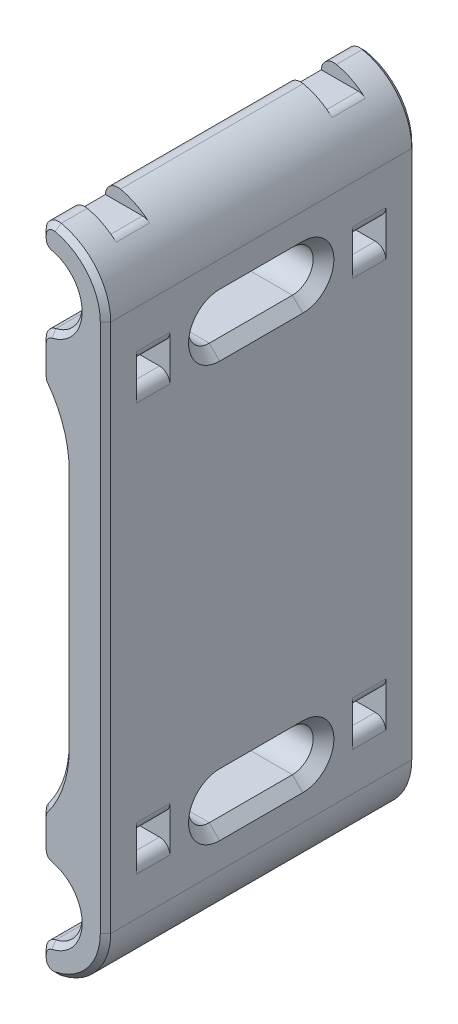
SolidWorks part; units mm, degrees
material "ABS"
ref_plane "Alzado" through (0, 0, 0) normal (0, 0, 1) x (1, 0, 0)
ref_plane "Planta" through (0, 0, 0) normal (0, 1, 0) x (1, 0, 0)
ref_plane "Vista lateral" through (0, 0, 0) normal (1, 0, 0) x (0, 0, -1)
sketch "Croquis1" plane through (0, 0, 0) normal (0, 0, 1) x (1, 0, 0)
  line L5 (-13.465, 0) -> (13.8234, 0) construction
  line L8 (-4, 17.4338) -> (-8.9869, 20.2963)
  line L9 (-4, 17.4338) -> (-4, -17.4338)
  line L10 (0, 25.5) -> (0, -25.5)
  line L11 (-4, -17.4338) -> (-8.9869, -20.2963)
  circle A0 centre (-6, 25.5) radius 3.25
  arc A5 (0, 25.5) -> (-8.9869, 20.2963) centre (-6, 25.5) ccw
  arc A6 (0, -25.5) -> (-8.9869, -20.2963) centre (-6, -25.5) cw
  circle A7 centre (-6, -25.5) radius 3.25
  point P7 (0, 0)
  point P15 (0, 0)
  point P16 (-4, 0)
  point P17 (-4, 0)
  dimension "D1" = 6.5
  dimension "D2" = 51
  dimension "D3" = 4
  dimension "D4" = 6
extrude "Saliente-Extruir1" add sketch "Croquis1" against normal blind 30
fillet "Redondeo1" radius 10 2 edges at (-4, -17.4338, -15) (-4, 17.4338, -15)
sketch "Croquis2" plane through (0, 0, 0) normal (1, 0, 0) x (0, 0, -1)
  line L0 (-8.2811, 0) -> (45.0775, 0) construction
  line L1 (11, 20) -> (19, 20) construction
  line L2 (11, 22) -> (19, 22)
  line L3 (11, 18) -> (19, 18)
  line L4 (11, -20) -> (19, -20) construction
  line L5 (11, -22) -> (19, -22)
  line L6 (11, -18) -> (19, -18)
  line L7 (0, 11.6436) -> (30, 11.6436) construction
  line L8 (30, 31.5) -> (0, 31.5) construction
  arc A0 (11, 22) -> (11, 18) centre (11, 20) ccw
  arc A1 (19, 18) -> (19, 22) centre (19, 20) ccw
  arc A2 (11, -22) -> (11, -18) centre (11, -20) cw
  arc A3 (19, -18) -> (19, -22) centre (19, -20) cw
  point P5 (15, 20)
  point P12 (15, -20)
  point P20 (15, 11.6436)
  point P22 (15, 20)
  dimension "D1" = 2
  dimension "D2" = 8
  dimension "D3" = 11.5
extrude "Cortar-Extruir1" cut sketch "Croquis2" against normal through all
sketch "Croquis3" plane through (0, 0, -30) normal (0, 0, -1) x (-1, 0, 0)
  line L1 (25.3768, -37.4523) -> (6.2082, -37.4523)
  line L2 (25.3768, -37.4523) -> (25.3768, 44.7692)
  line L3 (25.3768, 44.7692) -> (6.2082, 44.7692)
  line L4 (6.2082, -37.4523) -> (6.2082, 44.7692)
extrude "Cortar-Extruir2" cut sketch "Croquis3" against normal through all
sketch "Croquis4" plane through (-4, 0, 0) normal (-1, 0, 0) x (0, 0, 1)
  line L0 (12.0714, 0) -> (-39.4319, 0) construction
  line L1 (-30, -25.5) -> (0, -25.5) construction
  line L2 (-6.2, 32.5) -> (-6.2, 30.2)
  line L3 (-27, 32.5) -> (-23.8, 32.5)
  line L4 (-27, 32.5) -> (-27, 30.2)
  line L5 (-27, 30.2) -> (-23.8, 30.2)
  line L6 (-23.8, 32.5) -> (-23.8, 30.2)
  line L7 (-3, 30.2) -> (-6.2, 30.2)
  line L8 (-3, 32.5) -> (-3, 30.2)
  line L9 (-3, 32.5) -> (-6.2, 32.5)
  line L18 (-30, 25.5) -> (0, 25.5) construction
  line L19 (-23.8, 18.5) -> (-23.8, 20.8)
  line L20 (-27, 20.8) -> (-23.8, 20.8)
  line L21 (-27, 18.5) -> (-27, 20.8)
  line L22 (-27, 18.5) -> (-23.8, 18.5)
  line L23 (-3, 18.5) -> (-6.2, 18.5)
  line L24 (-3, 18.5) -> (-3, 20.8)
  line L25 (-3, 20.8) -> (-6.2, 20.8)
  line L26 (-6.2, 18.5) -> (-6.2, 20.8)
  line L27 (-6.2, -18.5) -> (-6.2, -20.8)
  line L36 (-30, 28.75) -> (-30, 22.25) construction
  line L37 (0, 31.4964) -> (0, 28.7433) construction
  line L38 (-3, -20.8) -> (-6.2, -20.8)
  line L39 (-3, -18.5) -> (-3, -20.8)
  line L40 (-3, -18.5) -> (-6.2, -18.5)
  line L41 (-27, -18.5) -> (-23.8, -18.5)
  line L42 (-27, -18.5) -> (-27, -20.8)
  line L43 (-27, -20.8) -> (-23.8, -20.8)
  line L44 (-23.8, -18.5) -> (-23.8, -20.8)
  line L45 (-3, -32.5) -> (-6.2, -32.5)
  line L46 (-3, -32.5) -> (-3, -30.2)
  line L47 (-3, -30.2) -> (-6.2, -30.2)
  line L48 (-23.8, -32.5) -> (-23.8, -30.2)
  line L49 (-27, -30.2) -> (-23.8, -30.2)
  line L50 (-27, -32.5) -> (-27, -30.2)
  line L51 (-27, -32.5) -> (-23.8, -32.5)
  line L52 (-6.2, -32.5) -> (-6.2, -30.2)
  line L53 (0, 22.25) -> (0, 28.75) construction
  line L54 (-15, 25.5) -> (-15, 34.8674) construction
  point P47 (-25.4, 20.8)
  dimension "D1" = 2.3
  dimension "D2" = 3
  dimension "D3" = 3.2
  dimension "D4" = 9.4
extrude "Cortar-Extruir7" cut sketch "Croquis4" against normal through all both and the other way through all
fillet "Redondeo2" radius 1.2 10 edges at (-6.2082, -31.4964, -28.5) (-6.2082, -31.4964, -1.5) (-6.2082, -22.2567, -15) (-6.2082, -28.7433, -15) (-6.2082, -17.9116, -15) (-6.2082, 17.9116, -15) (-6.2082, 31.4964, -1.5) (-6.2082, 31.4964, -28.5) (-6.2082, 28.7433, -15) (-6.2082, 22.2567, -15)
fillet "Redondeo4" radius 1 10 edges at (0, 20.8, -25.4) (0, 18.5, -25.4) (0, 18.5, -4.6) (0, 20.8, -4.6) (-2.2704, 30.2, -25.4) (-2.2704, 30.2, -4.6) (0, -18.5, -4.6) (0, -18.5, -25.4) (0, -20.8, -25.4) (0, -20.8, -4.6)
chamfer "Chamfer1" distance 0.5 angle 45 40 edges at (-5.9466, 29.0901, -30) (-2.75, 25.5, -30) (-5.9466, 21.9099, -30) (-6.2082, 19.7415, -30) (-6.1475, 17.9442, -30) (-4.5057, 14.7834, -30) (-4, 0, -30) (-4.5057, -14.7834, -30) (-6.1475, -17.9442, -30) (-6.2082, -19.7415, -30) (-5.9466, -21.9099, -30) (-2.75, -25.5, -30) (-5.9466, -29.0901, -30) (-6.2082, -30.0172, -30) (-5.764, -31.1285, -30) (-1.3396, -29.279, -30) (0, 0, -30) (-1.3396, 29.279, -30) (-5.764, 31.1285, -30) (-6.2082, 30.0172, -30) (-2.75, -25.5, 0) (-5.9466, -21.9099, 0) (-5.9466, -29.0901, 0) (-6.2082, -19.7415, 0) (-6.2082, -30.0172, 0) (-6.1475, -17.9442, 0) (-5.764, -31.1285, 0) (-4.5057, -14.7834, 0) (-1.3396, -29.279, 0) (-4, 0, 0) (0, 0, 0) (-4.5057, 14.7834, 0) (-1.3396, 29.279, 0) (-6.1475, 17.9442, 0) (-5.764, 31.1285, 0) (-6.2082, 19.7415, 0) (-6.2082, 30.0172, 0) (-5.9466, 21.9099, 0) (-5.9466, 29.0901, 0) (-2.75, 25.5, 0)
chamfer "Chamfer2" distance 1 angle 45 8 edges at (0, -20, -21) (0, -18, -15) (0, -22, -15) (0, -20, -9) (0, 18, -15) (0, 20, -21) (0, 20, -9) (0, 22, -15)
